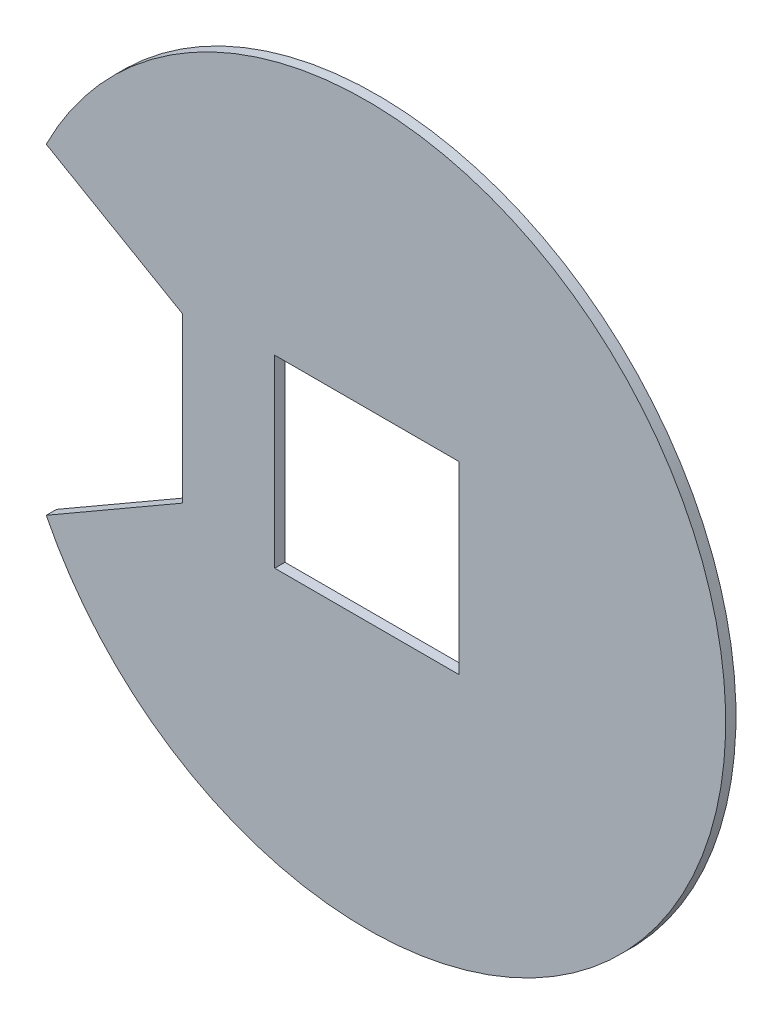
SolidWorks part; units mm, degrees
material "Balsa"
ref_plane "Plan de face" through (0, 0, 0) normal (0, 0, 1) x (1, 0, 0)
ref_plane "Plan de dessus" through (0, 0, 0) normal (0, 1, 0) x (1, 0, 0)
ref_plane "Plan de droite" through (0, 0, 0) normal (1, 0, 0) x (0, 0, -1)
sketch "Esquisse1" plane through (0, 0, 0) normal (0, 0, 1) x (1, 0, 0)
  line L0 (45, 45) -> (45, -45)
  line L1 (45, -45) -> (-45, -45)
  line L2 (-45, -45) -> (-45, 45)
  line L3 (-45, 45) -> (45, 45)
  line L8 (45, -45) -> (-45, 45) construction
  line L9 (-45, -45) -> (45, 45) construction
  circle A0 centre (0, 0) radius 175
  dimension "D2" = 350
  dimension "D3" = 90
  dimension "D1" = 90
extrude "Boss.-Extru.1" add sketch "Esquisse1" along normal blind 5
sketch "Esquisse2" plane through (0, 0, 5) normal (0, 0, 1) x (1, 0, 0)
  line L0 (-90, 0) -> (-49.5717, 0) construction
  line L1 (-156.4682, 78.3754) -> (-90, 40)
  line L2 (0, 0) -> (0, 175) construction
  line L3 (-90, 40) -> (-90, -40)
  line L4 (-90, -40) -> (-156.4682, -78.3754)
  circle A0 centre (0, 0) radius 175 construction
  arc A1 (-156.4682, 78.3754) -> (-156.4682, -78.3754) centre (0, 0) ccw
  dimension "D2" = 80
  dimension "D1" = 90
  dimension "D3" = 90
  dimension "D4" = 120
extrude "Enlèv. mat.-Extru.1" cut sketch "Esquisse2" against normal blind 10
